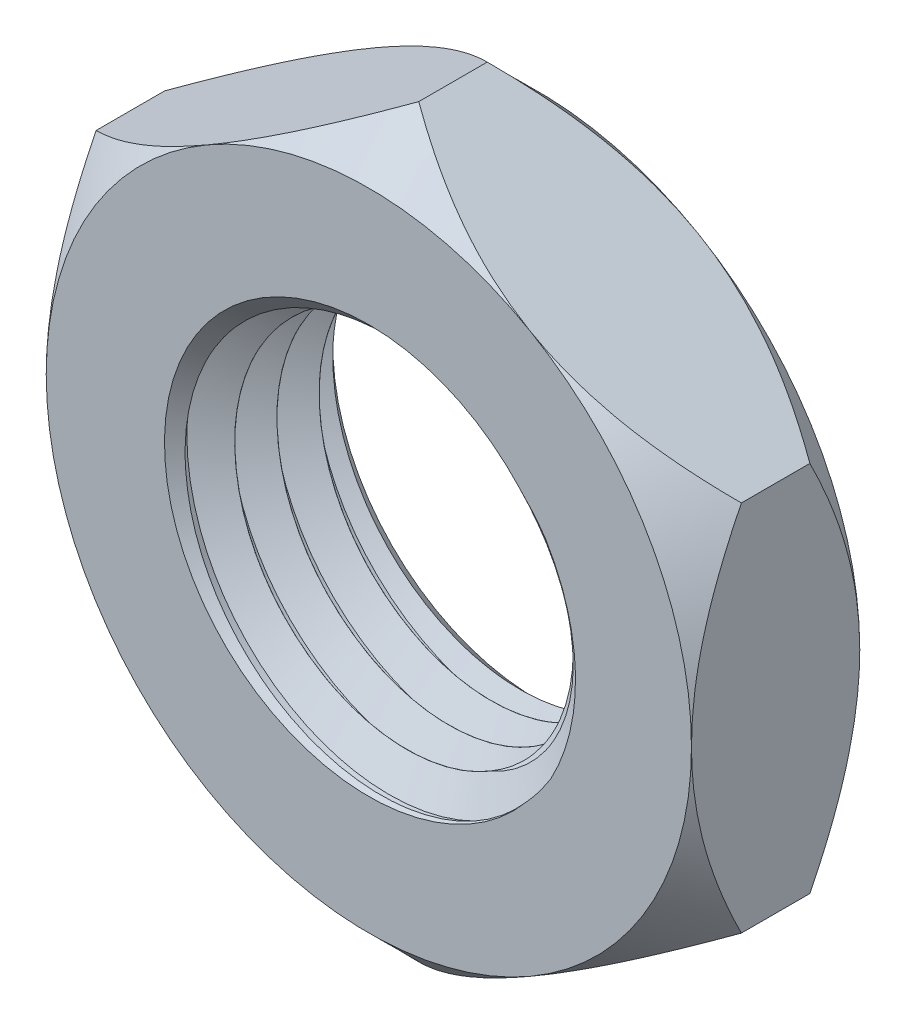
SolidWorks part; units mm, degrees
ref_plane "Front Plane" through (0, 0, 0) normal (1, 0, 0) x (0, 1, 0)
ref_plane "Top Plane" through (0, 0, 0) normal (0, 0, 1) x (0, 1, 0)
ref_plane "Right Plane" through (0, 0, 0) normal (0, 1, 0) x (-1, 0, 0)
sketch "Sketch1" plane through (0, 0, 0) normal (0, 0, 1) x (0, 1, 0)
  line L1 (6.6395, 0) -> (3.3198, 5.75)
  line L2 (3.3198, 5.75) -> (-3.3198, 5.75)
  line L3 (-3.3198, 5.75) -> (-6.6395, 0)
  line L4 (-6.6395, 0) -> (-3.3198, -5.75)
  line L5 (-3.3198, -5.75) -> (3.3198, -5.75)
  line L6 (3.3198, -5.75) -> (6.6395, 0)
  circle A0 centre (0, 0) radius 5.75 construction
  dimension "D2" = 11.5
extrude "Boss-Extrude1" add sketch "Sketch1" along normal mid plane 3
sketch "Sketch2" plane through (0, 0, 1.5) normal (0, 0, 1) x (1, 0, 0)
  line L0 (5.75, -3.3198) -> (5.75, 3.3198) construction
  line L1 (-5.75, 3.3198) -> (-5.75, -3.3198) construction
  circle A0 centre (0, 0) radius 5.75
extrude "Cut-Extrude1" cut sketch "Sketch2" against normal through all draft 45 flip side to cut
mirror "Mirror1" about plane through (0, 0, 0) normal (0, 0, 1) of "Cut-Extrude1"
sketch "Sketch3" plane through (0, 0, 1.5) normal (0, 0, 1) x (1, 0, 0)
  circle A0 centre (0, 0) radius 3.1425
  dimension "D1" = 6.285
extrude "Cut-Extrude2" cut sketch "Sketch3" against normal through all
chamfer "Chamfer1" distance 0.5 angle 45 2 edges at (3.1425, 0, -1.5) (3.1425, 0, 1.5)
thread "Thread1" pitch 1 method cut profile "Thread Profile5" start angle 0, offset 2, length 0, pitch 0.752, diameter 6.285
ref_plane "Plane5" through (-3.1425, 0, 3) normal (0, -1, 0) x (-1, 0, 0)
sketch "Thread Profile5" plane through (-3.1425, 0, 3) normal (0, -1, 0) x (-1, 0, 0)
  line L0 (0, 0) -> (0, 1) construction
  line L1 (0, 0) -> (0.5413, 0.3125)
  line L2 (0.5413, 0.3125) -> (0.5413, 0.4375)
  line L3 (0.5413, 0.4375) -> (0, 0.75)
  line L4 (0.5413, 0.375) -> (0, 0.375) construction
  line L11 (0, 0) -> (0, 0.75)
  point P2 (0, 0)
  dimension "Pitch" = 1
  dimension "Profile_Angle" = 60
  dimension "Profile_Land" = 0.125
  dimension "Profile_Height" = 0.5413
